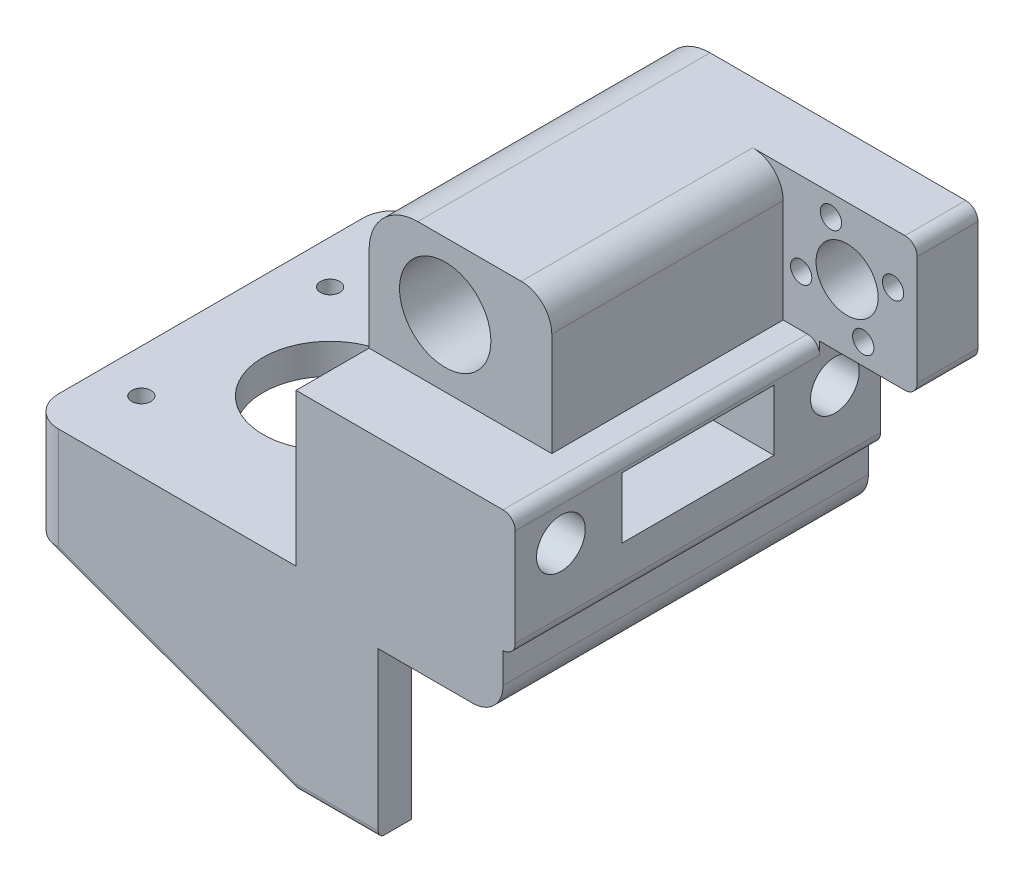
SolidWorks part; units mm, degrees
ref_plane "前视基准面" through (0, 0, 0) normal (0, 0, 1) x (1, 0, 0)
ref_plane "上视基准面" through (0, 0, 0) normal (0, 1, 0) x (1, 0, 0)
ref_plane "右视基准面" through (0, 0, 0) normal (1, 0, 0) x (0, 0, -1)
sketch "草图1" plane through (0, 0, 0) normal (0, 1, 0) x (1, 0, 0)
  line L1 (-40, 30) -> (40, 30)
  line L2 (-40, 30) -> (-40, -30)
  line L3 (-40, -30) -> (40, -30)
  line L4 (40, 30) -> (40, -30)
  line L5 (0, -30) -> (0, 30) construction
  line L6 (-40, 0) -> (40, 0) construction
  point P0 (0, 0)
  dimension "D1" = 80
  dimension "D2" = 60
extrude "凸台-拉伸1" add sketch "草图1" along normal blind 5
sketch "草图2" plane through (0, 5, 0) normal (0, 1, 0) x (1, 0, 0)
  line L0 (-40, 0) -> (40, 0) construction
  line L1 (-40, 30) -> (-40, -30) construction
  line L2 (40, -30) -> (40, 30) construction
  line L4 (-34, 15.5) -> (-3, 15.5) construction
  line L5 (-34, 15.5) -> (-34, -15.5) construction
  line L6 (-34, -15.5) -> (-3, -15.5) construction
  line L7 (-3, 15.5) -> (-3, -15.5) construction
  line L8 (-18.5, -15.5) -> (-18.5, 15.5) construction
  line L9 (-34, 0) -> (-3, 0) construction
  circle A0 centre (-3, 15.5) radius 1.75
  circle A1 centre (-3, -15.5) radius 1.75
  circle A2 centre (-34, -15.5) radius 1.75
  circle A3 centre (-34, 15.5) radius 1.75
  circle A4 centre (-18.5, 0) radius 11
  point P6 (-18.5, 0)
  dimension "D3" = 3.5
  dimension "D4" = 22
  dimension "D1" = 31
  dimension "D2" = 6
extrude "切除-拉伸1" cut sketch "草图2" against normal through all
sketch "草图3" plane through (0, 5, 0) normal (0, 1, 0) x (1, 0, 0)
  line L0 (4, 30) -> (4, -30)
  line L1 (40, 30) -> (-40, 30) construction
  line L2 (-40, -30) -> (40, -30) construction
  line L3 (4, -30) -> (40, -30)
  line L4 (40, -30) -> (40, 30)
  line L5 (40, 30) -> (4, 30)
  circle A0 centre (-3, 15.5) radius 1.75 construction
  dimension "D1" = 7
extrude "凸台-拉伸2" add sketch "草图3" along normal blind 15
sketch "草图4" plane through (4, 0, 0) normal (-1, 0, 0) x (0, 0, 1)
  line L0 (-30, 20) -> (-30, 5) construction
  line L1 (-30, 12.5) -> (30, 12.5) construction
  line L2 (30, 20) -> (30, 5) construction
  line L4 (-12.5, 17.5) -> (12.5, 17.5)
  line L5 (-12.5, 17.5) -> (-12.5, 7.5)
  line L6 (-12.5, 7.5) -> (12.5, 7.5)
  line L7 (12.5, 17.5) -> (12.5, 7.5)
  line L8 (0, 7.5) -> (0, 17.5) construction
  line L9 (-12.5, 12.5) -> (12.5, 12.5) construction
  circle A0 centre (-22.5, 12.5) radius 4
  circle A1 centre (22.5, 12.5) radius 4
  point P10 (0, 12.5)
  dimension "D1" = 8
  dimension "D2" = 45
  dimension "D3" = 7.5
  dimension "D4" = 25
  dimension "D5" = 10
extrude "切除-拉伸7" cut sketch "草图4" against normal through all
sketch "草图14" plane through (0, 20, 0) normal (0, 1, 0) x (1, 0, 0)
  line L0 (4, 30) -> (4, -18)
  line L1 (4, 30) -> (4, -30) construction
  line L2 (4, -18) -> (34, -18)
  line L3 (34, -18) -> (34, 20)
  line L4 (34, 20) -> (56, 20)
  line L5 (56, 20) -> (56, 30)
  line L6 (56, 30) -> (4, 30)
  dimension "D1" = 30
  dimension "D2" = 22
  dimension "D3" = 10
  dimension "D4" = 48
extrude "凸台-拉伸6" add sketch "草图14" along normal blind 22
sketch "草图15" plane through (0, 0, 18) normal (0, 0, 1) x (1, 0, 0)
  line L0 (4, 31) -> (29, 31) construction
  line L1 (4, 42) -> (4, 20) construction
  circle A0 centre (16.5, 31) radius 7.5
  dimension "D1" = 15
  dimension "D2" = 12.5
extrude "切除-拉伸8" cut sketch "草图15" against normal through all
sketch "草图16" plane through (0, 0, -20) normal (0, 0, 1) x (1, 0, 0)
  circle A4 centre (44.5, 31) radius 5.1
  circle A7 centre (16.5, 31) radius 7.5 construction
  dimension "D4" = 10.2
  dimension "D1" = 28
extrude "切除-拉伸9" cut sketch "草图16" against normal through all
fillet "圆角1" radius 8 1 edges at (4, 42, -6)
fillet "圆角2" radius 5 1 edges at (34, 42, -1)
fillet "圆角3" radius 2 1 edges at (56, 42, -25)
fillet "圆角4" radius 2 3 edges at (40, 20, 5) (40, 0, 0) (56, 20, -25)
ref_plane "基准面1" through (0, 0, 22) normal (0, 0, 1) x (1, 0, 0)
sketch "草图18" plane through (0, 0, -30) normal (0, 0, -1) x (-1, 0, 0)
  circle A0 centre (-41.8444, 38.5464) radius 1.75
  circle A1 centre (-36.9536, 28.3444) radius 1.75
  circle A2 centre (-47.1556, 23.4536) radius 1.75
  circle A3 centre (-52.0464, 33.6556) radius 1.75
sketch "草图20" plane through (0, 0, -30) normal (0, 0, -1) x (-1, 0, 0)
  circle A0 centre (-41.8444, 38.5464) radius 1.75
  circle A1 centre (-36.9536, 28.3444) radius 1.75
  circle A2 centre (-47.1556, 23.4536) radius 1.75
  circle A3 centre (-52.0464, 33.6556) radius 1.75
extrude "切除-拉伸11" cut sketch "草图20" against normal through all
ref_plane "基准面2" through (0, 2.5, 0) normal (0, 1, 0) x (1, 0, 0)
sketch "草图23" plane through (0, 0, 0) normal (0, -1, 0) x (1, 0, 0)
  line L4 (-40, -30) -> (38, -30)
  line L5 (38, -30) -> (38, 30)
  line L6 (38, 30) -> (-40, 30)
  line L7 (-40, 30) -> (-40, -30)
  line L8 (-40, -30) -> (38, -30)
  line L9 (38, -30) -> (38, 30)
  line L10 (38, 30) -> (-40, 30)
  line L11 (-40, 30) -> (-40, -30)
  dimension "D1" = 0
extrude "凸台-拉伸8" add sketch "草图23" along normal blind 10
sketch "草图26" plane through (0, 5, 0) normal (0, 1, 0) x (1, 0, 0)
  line L4 (4, -30) -> (4, 30)
  line L5 (4, 30) -> (-40, 30)
  line L6 (-40, 30) -> (-40, -30)
  line L7 (-40, -30) -> (4, -30)
  line L8 (4, -30) -> (4, 30)
  line L9 (4, 30) -> (-40, 30)
  line L10 (-40, 30) -> (-40, -30)
  line L11 (-40, -30) -> (4, -30)
  dimension "D1" = 0
extrude "切除-拉伸13" cut sketch "草图26" against normal blind 10
sketch "草图25" plane through (0, -10, 0) normal (0, -1, 0) x (1, 0, 0)
  line L0 (-1.9022, 18.5053) -> (-32.9022, -12.4947) construction
  line L5 (-1.9022, 18.5053) -> (-32.9022, 18.5053) construction
  line L6 (-1.9022, -12.4947) -> (-32.9022, 18.5053) construction
  line L12 (-32.9022, -12.4947) -> (-32.9022, 18.5053) construction
  line L13 (-1.9022, -12.4947) -> (-1.9022, 18.5053) construction
  line L14 (-1.9022, -12.4947) -> (-32.9022, -12.4947) construction
  circle A5 centre (-32.9022, -12.4947) radius 1.5818
  circle A6 centre (-1.9022, 18.5053) radius 1.5818
  circle A7 centre (-32.9022, 18.5053) radius 1.5818
  circle A9 centre (-1.9022, -12.4947) radius 1.5818
  circle A10 centre (-17.4022, 3.0053) radius 11
  point P26 (-16.1299, 27.4513)
  dimension "D1" = 22
ref_plane "基准面3" through (0, 0, 23) normal (0, 0, 1) x (1, 0, 0)
sketch "草图29" plane through (0, 0, 23) normal (0, 0, 1) x (1, 0, 0)
  line L1 (-40, -5) -> (-40, -21)
  line L2 (-40, -21) -> (4, -37)
  line L3 (4, -37) -> (4, -5)
  line L4 (4, -5) -> (-40, -5)
  dimension "D1" = 16
  dimension "D2" = 32
extrude "凸台-拉伸9" add sketch "草图29" along normal blind 5
fillet "圆角5" radius 5 3 edges at (38, -10, 0) (-40, -7.5, 30) (-40, -7.5, -30)
extrude "切除-拉伸14" cut sketch "草图25" against normal through all
sketch "草图30" plane through (0, 0, 23) normal (0, 0, -1) x (-1, 0, 0)
  line L1 (-4, -10) -> (39, -10) construction
  line L2 (-4, -37) -> (-4, -10) construction
  line L3 (39, -21.3636) -> (-4, -37) construction
  line L5 (-4, -10) -> (40, -10)
  line L6 (-4, -37) -> (-4, -10)
  line L7 (40, -21) -> (-4, -37)
  line L8 (40, -10) -> (40, -21) construction
  line L10 (40, -21) -> (40, -10)
extrude "切除-拉伸15" cut sketch "草图30" against normal blind 1.5
sketch "草图31" plane through (0, 0, 28) normal (0, 0, 1) x (1, 0, 0)
  line L0 (-39.7016, -21.1085) -> (-39.7016, -10)
  line L4 (4, -10) -> (-39, -10)
  line L5 (-39, -10) -> (-39, -21.3636)
  line L6 (-39, -21.3636) -> (4, -37)
  line L7 (4, -37) -> (4, -10)
  line L8 (4, -10) -> (-39.7016, -10)
  line L10 (-39.7016, -21.1085) -> (4, -37)
  line L11 (4, -37) -> (4, -10)
  dimension "D1" = 0
extrude "凸台-拉伸10" add sketch "草图31" along normal up to surface (2 mm away) up to face at (16.6864, 2.3964, 30)
fillet "圆角6" radius 1 4 edges at (-40, -15.5, 24.5) (-17.8508, -29.0543, 30) (-39.7016, -15.5543, 28) (-39.7016, -15.5543, 30)
sketch "草图32" plane through (0, -10, 0) normal (0, 1, 0) x (1, 0, 0)
  line L2 (-39.7016, -28.9544) -> (-39.7016, -29)
  line L3 (-38.7016, -30) -> (-35, -30)
  line L4 (-39.7016, -28.9544) -> (-39.7016, -29)
  line L5 (-38.7016, -30) -> (-35, -30)
  arc A3 (-39, -28) -> (-35, -30) centre (-35, -25) ccw
  arc A4 (-39, -28) -> (-39.7016, -28.9544) centre (-38.7016, -28.9544) ccw
  arc A5 (-39.7016, -29) -> (-38.7016, -30) centre (-38.7016, -29) ccw
  arc A6 (-39, -28) -> (-35, -30) centre (-35, -25) ccw
  arc A7 (-39, -28) -> (-39.7016, -28.9544) centre (-38.7016, -28.9544) ccw
  arc A8 (-39.7016, -29) -> (-38.7016, -30) centre (-38.7016, -29) ccw
  dimension "D1" = 0
extrude "切除-拉伸16" cut sketch "草图32" against normal through all
sketch "草图33" plane through (4, 0, 0) normal (1, 0, 0) x (0, 0, -1)
  line L4 (-30, -10) -> (-30, -35.9359)
  line L5 (-29, -37) -> (-24.5, -37)
  line L6 (-24.5, -37) -> (-24.5, -10)
  line L7 (-24.5, -10) -> (-30, -10)
  line L8 (-30, -10) -> (-30, -35.9359)
  line L9 (-29, -37) -> (-24.5, -37)
  line L10 (-24.5, -37) -> (-24.5, -10)
  line L11 (-24.5, -10) -> (-30, -10)
  ellipse E1 centre (-29, -35.9359) end of major axis (-29, -34.8719) minor radius 1 (-30, -35.9359) -> (-29, -37) ccw
  ellipse E2 centre (-29, -35.9359) end of major axis (-29, -34.8719) minor radius 1 (-30, -35.9359) -> (-29, -37) ccw
  dimension "D1" = 0
extrude "凸台-拉伸11" add sketch "草图33" along normal blind 13.5
